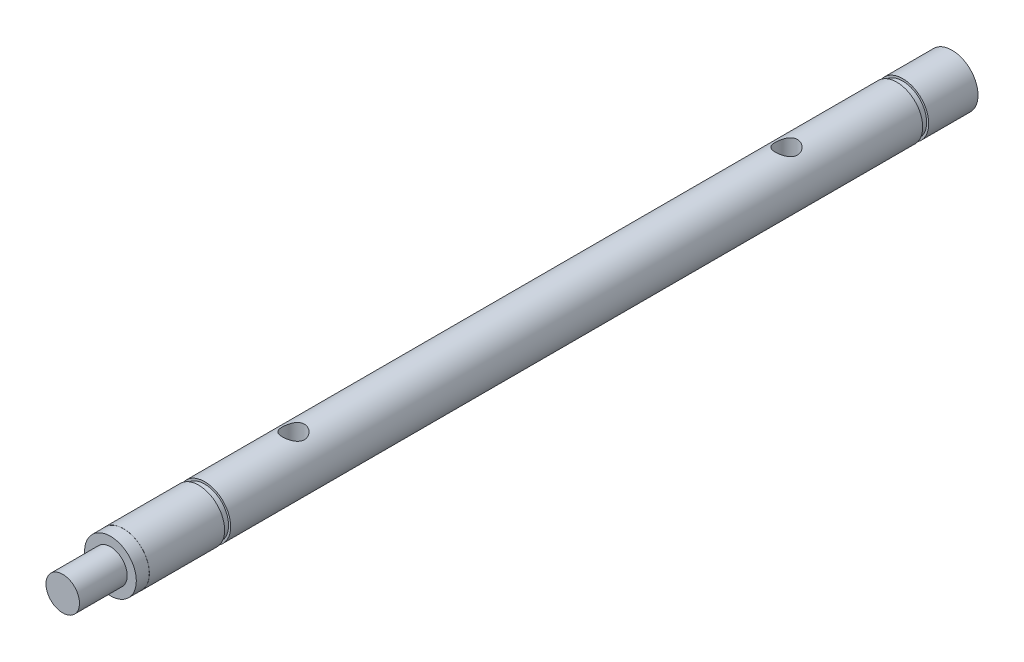
SolidWorks part; units mm, degrees
ref_plane "Front Plane" through (0, 0, 0) normal (0, 0, 1) x (1, 0, 0)
ref_plane "Top Plane" through (0, 0, 0) normal (0, 1, 0) x (1, 0, 0)
ref_plane "Right Plane" through (0, 0, 0) normal (1, 0, 0) x (0, 0, -1)
sketch "Sketch1" plane through (0, 0, 0) normal (0, 1, 0) x (1, 0, 0)
  line L0 (3.175, 99.7956) -> (-3.175, 99.7956) construction
  line L1 (4.915, -9.017) -> (-4.915, -9.017) construction
  line L2 (2.05, -1.5875) -> (2.05, -9.017) construction
  line L3 (4.915, -3.175) -> (-4.915, -3.175) construction
  line L4 (3.1623, -1.5875) -> (3.1623, -3.175) construction
  line L5 (3.175, -1.5875) -> (-3.175, -1.5875) construction
  line L6 (0, -1.5875) -> (0, 99.7956) construction
  line L7 (3.175, -1.5875) -> (3.175, 99.7956) construction
  line L8 (3.175, 99.7956) -> (0, 99.7956)
  line L9 (2.05, -9.017) -> (0, -9.017)
  line L10 (2.05, -3.175) -> (2.05, -9.017)
  line L11 (3.1623, -3.175) -> (2.05, -3.175)
  line L12 (3.1623, -1.5875) -> (3.1623, -3.175)
  line L13 (3.175, -1.5875) -> (3.1623, -1.5875)
  line L14 (0, -9.017) -> (0, 99.7956)
  line L15 (3.175, -1.5875) -> (3.175, 7.62)
  line L16 (3.175, 7.62) -> (2.921, 7.62) construction
  line L17 (2.921, 7.62) -> (2.921, 8.3566) construction
  line L18 (3.175, 8.3566) -> (2.921, 8.3566) construction
  line L19 (3.175, 93.0328) -> (2.921, 93.0328) construction
  line L20 (2.921, 93.7694) -> (2.921, 93.0328) construction
  line L21 (3.175, 93.7694) -> (2.921, 93.7694) construction
  line L22 (3.175, 7.62) -> (2.921, 7.62)
  line L23 (2.921, 7.62) -> (2.921, 8.3566)
  line L24 (3.175, 8.3566) -> (2.921, 8.3566)
  line L25 (3.175, 93.0328) -> (2.921, 93.0328)
  line L26 (2.921, 93.7694) -> (2.921, 93.0328)
  line L27 (3.175, 93.7694) -> (2.921, 93.7694)
  line L28 (3.175, 8.3566) -> (3.175, 93.0328)
  line L29 (3.175, 93.7694) -> (3.175, 99.7956)
  line L30 (4.7625, 14.4433) -> (-4.7625, 14.4433) construction
  line L31 (4.7625, 23.9683) -> (4.7625, 14.4433) construction
  line L32 (-4.7625, 23.9683) -> (-4.7625, 14.4433) construction
  line L33 (11.9063, 23.9683) -> (-11.9062, 23.9683) construction
  line L34 (4.7625, 74.7683) -> (4.7625, 84.2933) construction
  line L35 (-4.7625, 74.7683) -> (-4.7625, 84.2933) construction
  line L36 (4.7625, 84.2933) -> (-4.7625, 84.2933) construction
  line L37 (-4.7625, 74.7683) -> (4.7625, 74.7683) construction
  line L38 (4.7625, 14.4433) -> (-4.7625, 14.4433)
  line L39 (4.7625, 23.9683) -> (4.7625, 14.4433)
  line L40 (-4.7625, 23.9683) -> (-4.7625, 14.4433)
  line L41 (4.7625, 23.9683) -> (-4.7625, 23.9683)
  line L42 (4.7625, 74.7683) -> (4.7625, 84.2933)
  line L43 (-4.7625, 74.7683) -> (-4.7625, 84.2933)
  line L44 (4.7625, 84.2933) -> (-4.7625, 84.2933)
  line L45 (-4.7625, 74.7683) -> (4.7625, 74.7683)
  line L46 (0, 84.2933) -> (0, 74.7683) construction
  line L47 (0, 23.9683) -> (0, 14.4433) construction
  point P38 (0, 79.5308)
  point P39 (0, 19.2058)
  point P40 (0, 0)
  point P41 (0, 74.7683)
  point P42 (-0.0121, 84.2933)
  point P43 (0, 0)
  point P44 (0, 0)
  point P45 (0, 0)
  point P46 (0.0798, 23.9683)
  point P47 (0, 0)
revolve "Revolve1" add sketch "Sketch1" angle 360 about L14 region at (1.5819, 0, -92.0392) region at (1.5875, 0, -79.5308) region at (1.5875, 0, -49.3683) region at (1.5875, 0, -19.2058) region at (1.4835, 0, -3.5552)
ref_plane "Plane1" through (0, -3.175, 0) normal (0, -1, 0) x (-1, 0, 0)
hole_wizard "#6-32 Tapped Hole1" positions "Sketch2" profile "Sketch3" tap size "#6-32" standard "ANSI Inch"
sketch "Sketch2" plane through (0, -3.175, 0) normal (0, -1, 0) x (-1, 0, 0)
  point P0 (0, 79.5308)
  point P2 (0, 19.2058)
  point P7 (0, 0)
  point P8 (0, 0)
  point P10 (0, 0)
sketch "Sketch3" plane through (0, -3.175, -79.5308) normal (1, 0, 0) x (0, 0, -1)
  line L0 (0, 0) -> (0, 10.2107)
  line L1 (0, 10.2107) -> (1.3525, 9.398)
  line L2 (1.3525, 9.398) -> (1.3525, 0)
  line L5 (1.3525, 0) -> (0, 0)
  line L10 (0, 10.2107) -> (-1.3525, 9.398) construction
  line L11 (0, -6.35) -> (0, 107.95) construction
  dimension "Tap Drill Dia." = 2.7051
  dimension "Tap Drill Depth" = 9.398
  dimension "Drill Angle" = 118
cosmetic thread "Hole Thread2" parameters "D1"=6.35, "D2"=3.5052
cosmetic thread "Hole Thread3" parameters "D1"=6.35, "D2"=3.5052
